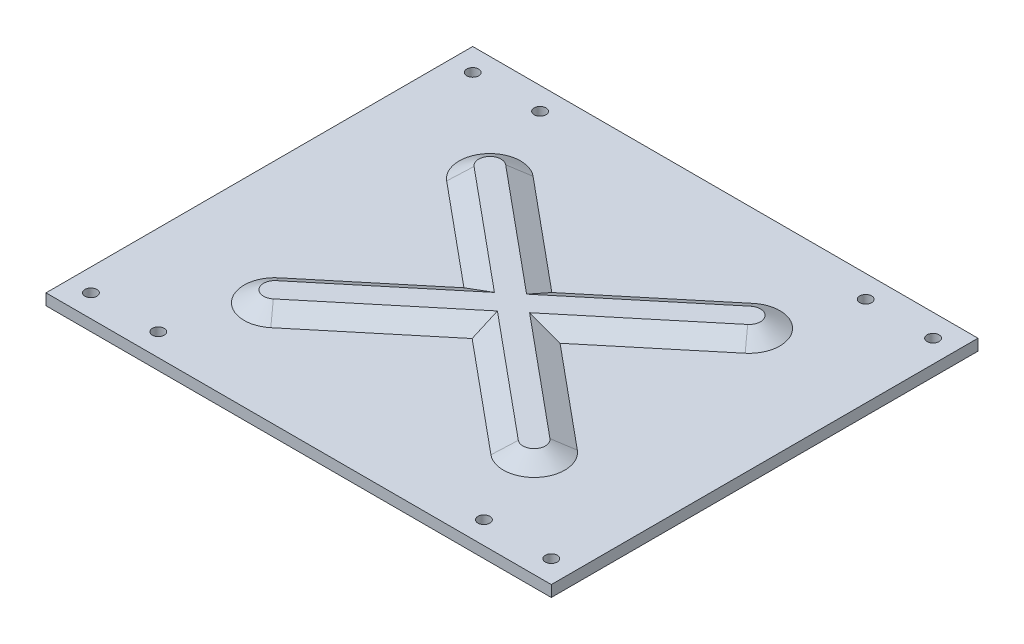
SolidWorks part; units mm, degrees
ref_plane "Front Plane" through (0, 0, 0) normal (0, 0, 1) x (1, 0, 0)
ref_plane "Top Plane" through (0, 0, 0) normal (0, 1, 0) x (1, 0, 0)
ref_plane "Right Plane" through (0, 0, 0) normal (1, 0, 0) x (0, 0, -1)
sketch "Sketch1" plane through (0, 0, 0) normal (0, 1, 0) x (1, 0, 0)
  line L0 (0, 180) -> (225, 180) construction
  line L1 (0, 0) -> (225, 0)
  line L2 (0, 0) -> (0, 190)
  line L3 (0, 190) -> (225, 190)
  line L4 (225, 0) -> (225, 190)
  line L5 (0, 95) -> (225, 95) construction
  circle A0 centre (10, 180) radius 2.65
  circle A1 centre (40, 180) radius 2.65
  circle A2 centre (185, 180) radius 2.65
  circle A3 centre (215, 180) radius 2.65
  circle A4 centre (215, 10) radius 2.65
  circle A5 centre (185, 10) radius 2.65
  circle A6 centre (40, 10) radius 2.65
  circle A7 centre (10, 10) radius 2.65
  dimension "D4" = 5.3
  dimension "D1" = 190
  dimension "D2" = 225
  dimension "D3" = 10
  dimension "D5" = 10
  dimension "D6" = 30
  dimension "D7" = 30
  dimension "D8" = 10
extrude "Boss-Extrude1" add sketch "Sketch1" along normal blind 5
sketch "Sketch2" plane through (0, 5, 0) normal (0, 1, 0) x (1, 0, 0)
  line L0 (10, 180) -> (215, 10) construction
  line L1 (54.7682, 142.8752) -> (170.2318, 47.1248) construction
  line L2 (51.5765, 139.0264) -> (167.0402, 43.276)
  line L3 (57.9598, 146.724) -> (173.4235, 50.9736)
  arc A0 (51.5765, 139.0264) -> (57.9598, 146.724) centre (54.7682, 142.8752) cw
  arc A1 (167.0402, 43.276) -> (173.4235, 50.9736) centre (170.2318, 47.1248) ccw
  point P8 (112.5, 95)
  dimension "D3" = 150
  dimension "D1" = 5
  dimension "D2" = 5
extrude "Boss-Extrude2" add sketch "Sketch2" along normal blind 5
ref_plane "Plane1" through (0, 0, -95) normal (0, 0, -1) x (-1, 0, 0)
mirror "Mirror1" about plane through (0, 0, -95) normal (0, 0, -1) of "Boss-Extrude2"
chamfer "Chamfer1" distance 5 angle 60 12 edges at (139.7701, 5, -65.8902) (174.0806, 5, -43.9331) (146.8782, 5, -72.9868) (146.8782, 5, -117.0132) (174.0806, 5, -146.0669) (139.7701, 5, -124.1098) (85.2299, 5, -124.1098) (85.2299, 5, -65.8902) (50.9194, 5, -146.0669) (50.9194, 5, -43.9331) (78.1218, 5, -117.0132) (78.1218, 5, -72.9868) first distance on face at (139.7701, 7.5, -65.8902) first distance on face at (172.1562, 7.5, -45.529) first distance on face at (146.8782, 7.5, -72.9868) first distance on face at (146.8782, 7.5, -117.0132) first distance on face at (172.1562, 7.5, -144.471) first distance on face at (139.7701, 7.5, -124.1098) first distance on face at (85.2299, 7.5, -124.1098) first distance on face at (85.2299, 7.5, -65.8902) first distance on face at (52.8438, 7.5, -144.471) first distance on face at (52.8438, 7.5, -45.529) first distance on face at (78.1218, 7.5, -117.0132) first distance on face at (78.1218, 7.5, -72.9868)
